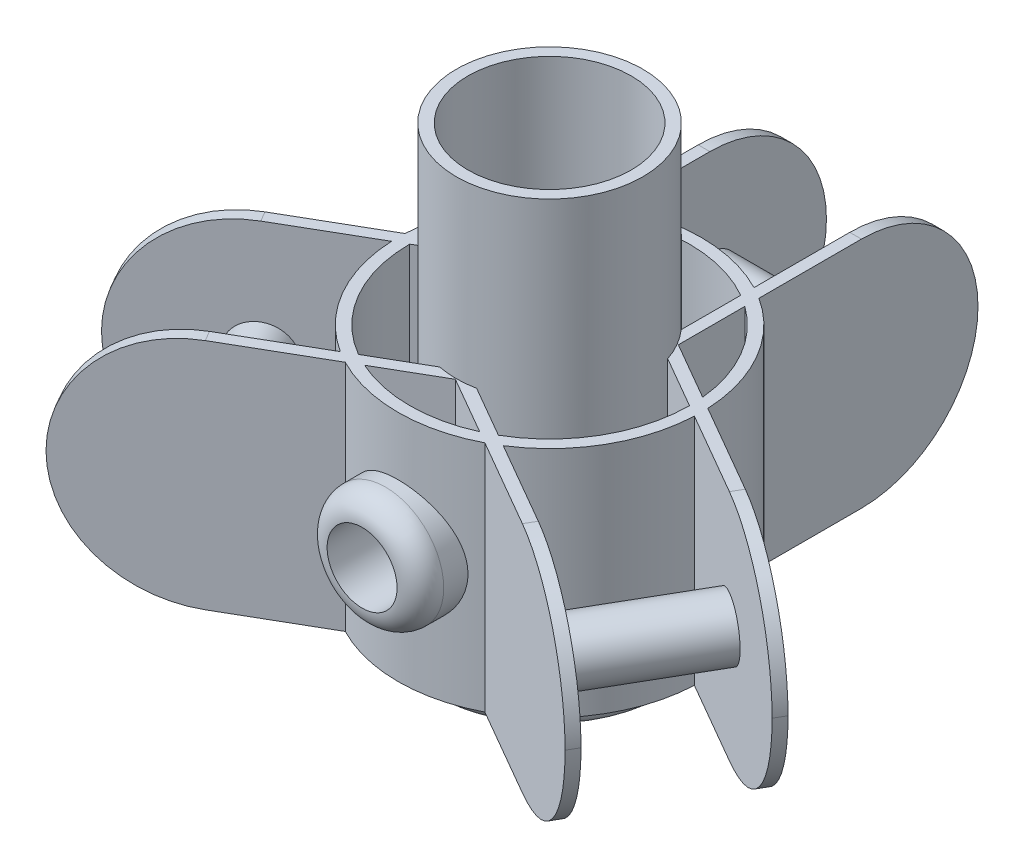
SolidWorks part; units mm, degrees
material "Rubber"
ref_plane "Front Plane" through (0, 0, 0) normal (0, 0, 1) x (1, 0, 0)
ref_plane "Top Plane" through (0, 0, 0) normal (0, 1, 0) x (1, 0, 0)
ref_plane "Right Plane" through (0, 0, 0) normal (1, 0, 0) x (0, 0, -1)
sketch "Sketch1" plane through (0, 0, 0) normal (0, 1, 0) x (1, 0, 0)
  line L0 (-6, 11.5326) -> (-6, 29.7468)
  line L1 (-6, 29.7468) -> (-7, 29.7468)
  line L2 (-7, 4.0415) -> (-7, 9.7468)
  line L3 (-7, 10.9545) -> (-7, 29.7468)
  line L4 (6, 10.3923) -> (6, 5.2915)
  line L5 (7, 4.0415) -> (7, 9.7468)
  line L6 (7, 10.9545) -> (7, 29.7468)
  line L7 (7, 29.7468) -> (6, 29.7468)
  line L8 (-29.2615, -8.8112) -> (-28.7615, -9.6772)
  line L9 (-6, 5.2915) -> (-6, 10.3923)
  line L10 (7, 29.7468) -> (6, 29.7468)
  line L11 (6, 29.7468) -> (6, 11.5326)
  line L12 (7.5826, 2.5504) -> (12, 0)
  line L13 (0, -8.0829) -> (4.941, -10.9356)
  line L14 (7, 4.0415) -> (11.941, 1.1888)
  line L15 (12.9868, 0.585) -> (29.2615, -8.8112)
  line L16 (12.9875, -0.5701) -> (28.7615, -9.6772)
  line L17 (22.7615, -20.0695) -> (6.9875, -10.9624)
  line L18 (5.9868, -11.5394) -> (22.2615, -20.9356)
  line L19 (6, -10.3923) -> (1.5826, -7.8419)
  line L20 (-1.5826, -7.8419) -> (-6, -10.3923)
  line L21 (-7, 4.0415) -> (-11.941, 1.1888)
  line L22 (0, -8.0829) -> (-4.941, -10.9356)
  line L23 (-5.9868, -11.5394) -> (-22.2615, -20.9356)
  line L24 (-6.9875, -10.9624) -> (-22.7615, -20.0695)
  line L25 (-28.7615, -9.6772) -> (-12.9875, -0.5701)
  line L26 (-12.9868, 0.585) -> (-29.2615, -8.8112)
  line L27 (-12, 0) -> (-7.5826, 2.5504)
  line L28 (-22.7615, -20.0695) -> (-22.2615, -20.9356)
  line L29 (22.2615, -20.9356) -> (22.7615, -20.0695)
  line L30 (28.7615, -9.6772) -> (29.2615, -8.8112)
  circle A0 centre (0, 0) radius 7
  arc A1 (-7.5826, 2.5504) -> (-1.5826, -7.8419) centre (0, 0) ccw
  arc A2 (-7, 9.7468) -> (-11.941, 1.1888) centre (0, 0) ccw
  arc A3 (-7, 10.9545) -> (-12.9868, 0.585) centre (0, 0) ccw
  arc A4 (6, 5.2915) -> (-6, 5.2915) centre (0, 0) ccw
  arc A5 (6, 10.3923) -> (-6, 10.3923) centre (0, 0) ccw
  arc A6 (6, 11.5326) -> (-6, 11.5326) centre (0, 0) ccw
  arc A7 (6, 5.2915) -> (-6, 5.2915) centre (0, 0) ccw
  arc A8 (11.941, 1.1888) -> (7, 9.7468) centre (0, 0) ccw
  arc A9 (1.5826, -7.8419) -> (7.5826, 2.5504) centre (0, 0) ccw
  arc A10 (-4.941, -10.9356) -> (4.941, -10.9356) centre (0, 0) ccw
  arc A11 (-5.9868, -11.5394) -> (5.9868, -11.5394) centre (0, 0) ccw
  arc A12 (-4.941, -10.9356) -> (4.941, -10.9356) centre (0, 0) ccw
  arc A13 (-4.941, -10.9356) -> (4.941, -10.9356) centre (0, 0) ccw
  arc A14 (6, -10.3923) -> (12, 0) centre (0, 0) ccw
  arc A15 (6, -10.3923) -> (12, 0) centre (0, 0) ccw
  arc A16 (6.9875, -10.9624) -> (12.9875, -0.5701) centre (0, 0) ccw
  arc A17 (1.5826, -7.8419) -> (7.5826, 2.5504) centre (0, 0) ccw
  arc A18 (-12, 0) -> (-6, -10.3923) centre (0, 0) ccw
  arc A19 (-12, 0) -> (-6, -10.3923) centre (0, 0) ccw
  arc A20 (-12.9875, -0.5701) -> (-6.9875, -10.9624) centre (0, 0) ccw
  arc A21 (-7.5826, 2.5504) -> (-1.5826, -7.8419) centre (0, 0) ccw
  arc A22 (6, 5.2915) -> (-6, 5.2915) centre (0, 0) ccw
  arc A23 (6, 10.3923) -> (-6, 10.3923) centre (0, 0) ccw
  arc A24 (6, 10.3923) -> (-6, 10.3923) centre (0, 0) ccw
  arc A25 (-7, 9.7468) -> (-11.941, 1.1888) centre (0, 0) ccw
  arc A26 (-7, 9.7468) -> (-11.941, 1.1888) centre (0, 0) ccw
  arc A27 (11.941, 1.1888) -> (7, 9.7468) centre (0, 0) ccw
  arc A28 (11.941, 1.1888) -> (7, 9.7468) centre (0, 0) ccw
  arc A29 (12.9868, 0.585) -> (7, 10.9545) centre (0, 0) ccw
  dimension "D1" = 3
extrude "Boss-Extrude1" add sketch "Sketch1" along normal blind 20 contours L15 A29 L6 L7 L11 A6 L0 L1 L3 A3 L26 L8 L25 A20 L24 L28 L23 A11 L18 L29 L17 A16 L16 L30 A0 A2 L2 L21 A5 L4 A4 L9 A8 L14 L5 A10 L22 L13 A14 L19 A9 L12 A18 L27 region at (0, 0, -12.2258)
fillet "Fillet1" radius 10 12 edges at (29.0115, 20, 9.2442) (29.0115, 0, 9.2442) (22.5115, 0, 20.5026) (22.5115, 20, 20.5026) (-29.0115, 0, 9.2442) (-22.5115, 0, 20.5026) (-22.5115, 20, 20.5026) (-29.0115, 20, 9.2442) (6.5, 0, -29.7468) (6.5, 20, -29.7468) (-6.5, 0, -29.7468) (-6.5, 20, -29.7468)
sketch "Sketch2" plane through (0, 0, 0) normal (0, -1, 0) x (1, 0, 0)
  circle A0 centre (0, 0) radius 13
extrude "Boss-Extrude2" add sketch "Sketch2" against normal blind 1
sketch "Sketch3" plane through (0, 20, 0) normal (0, 1, 0) x (1, 0, 0)
  circle A0 centre (0, 0) radius 7
  circle A1 centre (0, 0) radius 8
extrude "Boss-Extrude3" add sketch "Sketch3" along normal blind 15
sketch "Sketch4" plane through (-3, 0, -5.1962) normal (0.5, 0, 0.866) x (0.866, 0, -0.5)
  circle A0 centre (-19.7468, 10) radius 2.5
extrude "Boss-Extrude4" add sketch "Sketch4" along normal blind 12
pattern_circular "CirPattern1" count 3 every 120 about axis through (0, 0, 0) along (0, 1, 0) of "Boss-Extrude4"
ref_plane "Plane1" through (0, 0, 0) normal (-0.5, 0, 0.866) x (0.866, 0, 0.5)
ref_plane "Plane2" through (0, 0, 8.0829) normal (0, 0, -1) x (0, -1, 0)
ref_plane "Plane3" through (0, 0, 16.0829) normal (0, 0, -1) x (0, -1, 0)
sketch "Sketch5" plane through (0, 0, 16.0829) normal (0, 0, -1) x (0, -1, 0)
  circle A0 centre (-10, 0) radius 5
extrude "Boss-Extrude5" add sketch "Sketch5" along normal up to surface (4.0829 mm away) up to face at (0, 10, 12.2697)
fillet "Fillet2" radius 2 1 edges at (-5, 10, 16.0829)
sketch "Sketch6" plane through (0, 0, 16.0829) normal (0, 0, 1) x (1, 0, 0)
  circle A0 centre (0, 10) radius 3
extrude "Cut-Extrude1" cut sketch "Sketch6" against normal blind 12
cosmetic thread "Cosmetic Thread1" parameters "D2"=7
sketch "Sketch7" plane through (0, 0, 0) normal (0, -1, 0) x (1, 0, 0)
  circle A0 centre (0, 0) radius 6
  circle A1 centre (0, 0) radius 10
extrude "Boss-Extrude6" add sketch "Sketch7" along normal blind 3
fillet "Fillet3" radius 1 1 edges at (0, -3, -10)
sketch "Sketch8" plane through (0, -3, 0) normal (0, -1, 0) x (1, 0, 0)
  line L0 (4.7799, 6.4105) -> (3.5866, 4.81)
  line L1 (0, 8.5) -> (-0.4377, 8.5)
  line L2 (0, 8.5) -> (0.4377, 8.5)
  line L3 (0.9343, 7.9416) -> (0.701, 5.9589)
  line L4 (-0.9343, 7.9416) -> (-0.701, 5.9589)
  line L5 (4.25, 7.3612) -> (3.8709, 7.5801)
  line L6 (4.25, 7.3612) -> (4.6291, 7.1424)
  line L7 (3.1617, 7.3448) -> (2.3723, 5.5111)
  line L8 (7.3448, 3.1617) -> (5.5111, 2.3723)
  line L9 (7.3612, 4.25) -> (7.1424, 4.6291)
  line L10 (7.3612, 4.25) -> (7.5801, 3.8709)
  line L11 (6.4105, 4.7799) -> (4.81, 3.5866)
  line L12 (7.9416, -0.9343) -> (5.9589, -0.701)
  line L13 (8.5, 0) -> (8.5, 0.4377)
  line L14 (8.5, 0) -> (8.5, -0.4377)
  line L15 (7.9416, 0.9343) -> (5.9589, 0.701)
  line L16 (6.4105, -4.7799) -> (4.81, -3.5866)
  line L17 (7.3612, -4.25) -> (7.5801, -3.8709)
  line L18 (7.3612, -4.25) -> (7.1424, -4.6291)
  line L19 (7.3448, -3.1617) -> (5.5111, -2.3723)
  line L20 (3.1617, -7.3448) -> (2.3723, -5.5111)
  line L21 (4.25, -7.3612) -> (4.6291, -7.1424)
  line L22 (4.25, -7.3612) -> (3.8709, -7.5801)
  line L23 (4.7799, -6.4105) -> (3.5866, -4.81)
  line L24 (-0.9343, -7.9416) -> (-0.701, -5.9589)
  line L25 (0, -8.5) -> (0.4377, -8.5)
  line L26 (0, -8.5) -> (-0.4377, -8.5)
  line L27 (0.9343, -7.9416) -> (0.701, -5.9589)
  line L28 (-4.7799, -6.4105) -> (-3.5866, -4.81)
  line L29 (-4.25, -7.3612) -> (-3.8709, -7.5801)
  line L30 (-4.25, -7.3612) -> (-4.6291, -7.1424)
  line L31 (-3.1617, -7.3448) -> (-2.3723, -5.5111)
  line L32 (-7.3448, -3.1617) -> (-5.5111, -2.3723)
  line L33 (-7.3612, -4.25) -> (-7.1424, -4.6291)
  line L34 (-7.3612, -4.25) -> (-7.5801, -3.8709)
  line L35 (-6.4105, -4.7799) -> (-4.81, -3.5866)
  line L36 (-7.9416, 0.9343) -> (-5.9589, 0.701)
  line L37 (-8.5, 0) -> (-8.5, -0.4377)
  line L38 (-8.5, 0) -> (-8.5, 0.4377)
  line L39 (-7.9416, -0.9343) -> (-5.9589, -0.701)
  line L40 (-6.4105, 4.7799) -> (-4.81, 3.5866)
  line L41 (-7.3612, 4.25) -> (-7.5801, 3.8709)
  line L42 (-7.3612, 4.25) -> (-7.1424, 4.6291)
  line L43 (-7.3448, 3.1617) -> (-5.5111, 2.3723)
  line L44 (-3.1617, 7.3448) -> (-2.3723, 5.5111)
  line L45 (-4.25, 7.3612) -> (-4.6291, 7.1424)
  line L46 (-4.25, 7.3612) -> (-3.8709, 7.5801)
  line L47 (-4.7799, 6.4105) -> (-3.5866, 4.81)
  arc A0 (0.701, 5.9589) -> (-0.701, 5.9589) centre (0, 0) ccw
  circle A1 centre (0, 0) radius 6 construction
  arc A2 (-0.4377, 8.5) -> (-0.9343, 7.9416) centre (-0.4377, 8) ccw
  arc A3 (0.4377, 8.5) -> (0.9343, 7.9416) centre (0.4377, 8) cw
  arc A4 (4.6291, 7.1424) -> (4.7799, 6.4105) centre (4.3791, 6.7093) cw
  arc A5 (3.8709, 7.5801) -> (3.1617, 7.3448) centre (3.6209, 7.1471) ccw
  arc A6 (7.5801, 3.8709) -> (7.3448, 3.1617) centre (7.1471, 3.6209) cw
  arc A7 (7.1424, 4.6291) -> (6.4105, 4.7799) centre (6.7093, 4.3791) ccw
  arc A8 (8.5, -0.4377) -> (7.9416, -0.9343) centre (8, -0.4377) cw
  arc A9 (8.5, 0.4377) -> (7.9416, 0.9343) centre (8, 0.4377) ccw
  arc A10 (7.1424, -4.6291) -> (6.4105, -4.7799) centre (6.7093, -4.3791) cw
  arc A11 (7.5801, -3.8709) -> (7.3448, -3.1617) centre (7.1471, -3.6209) ccw
  arc A12 (3.8709, -7.5801) -> (3.1617, -7.3448) centre (3.6209, -7.1471) cw
  arc A13 (4.6291, -7.1424) -> (4.7799, -6.4105) centre (4.3791, -6.7093) ccw
  arc A14 (-0.4377, -8.5) -> (-0.9343, -7.9416) centre (-0.4377, -8) cw
  arc A15 (0.4377, -8.5) -> (0.9343, -7.9416) centre (0.4377, -8) ccw
  arc A16 (-4.6291, -7.1424) -> (-4.7799, -6.4105) centre (-4.3791, -6.7093) cw
  arc A17 (-3.8709, -7.5801) -> (-3.1617, -7.3448) centre (-3.6209, -7.1471) ccw
  arc A18 (-7.5801, -3.8709) -> (-7.3448, -3.1617) centre (-7.1471, -3.6209) cw
  arc A19 (-7.1424, -4.6291) -> (-6.4105, -4.7799) centre (-6.7093, -4.3791) ccw
  arc A20 (-8.5, 0.4377) -> (-7.9416, 0.9343) centre (-8, 0.4377) cw
  arc A21 (-8.5, -0.4377) -> (-7.9416, -0.9343) centre (-8, -0.4377) ccw
  arc A22 (-7.1424, 4.6291) -> (-6.4105, 4.7799) centre (-6.7093, 4.3791) cw
  arc A23 (-7.5801, 3.8709) -> (-7.3448, 3.1617) centre (-7.1471, 3.6209) ccw
  arc A24 (-3.8709, 7.5801) -> (-3.1617, 7.3448) centre (-3.6209, 7.1471) cw
  arc A25 (-4.6291, 7.1424) -> (-4.7799, 6.4105) centre (-4.3791, 6.7093) ccw
  arc A26 (5.9589, -0.701) -> (5.9589, 0.701) centre (0, 0) ccw
  arc A27 (4.81, -3.5866) -> (5.5111, -2.3723) centre (0, 0) ccw
  arc A28 (2.3723, -5.5111) -> (3.5866, -4.81) centre (0, 0) ccw
  arc A29 (-0.701, -5.9589) -> (0.701, -5.9589) centre (0, 0) ccw
  arc A30 (-3.5866, -4.81) -> (-2.3723, -5.5111) centre (0, 0) ccw
  arc A31 (-5.5111, -2.3723) -> (-4.81, -3.5866) centre (0, 0) ccw
  arc A32 (-5.9589, 0.701) -> (-5.9589, -0.701) centre (0, 0) ccw
  arc A33 (-4.81, 3.5866) -> (-5.5111, 2.3723) centre (0, 0) ccw
  arc A34 (3.5866, 4.81) -> (2.3723, 5.5111) centre (0, 0) ccw
  arc A35 (5.5111, 2.3723) -> (4.81, 3.5866) centre (0, 0) ccw
  arc A36 (-2.3723, 5.5111) -> (-3.5866, 4.81) centre (0, 0) ccw
  dimension "D1" = 0.5
  dimension "D2" = 12
extrude "Boss-Extrude7" add sketch "Sketch8" along normal blind 0.25
sketch "Sketch9" plane through (0, 0, 0) normal (0, -1, 0) x (1, 0, 0)
  circle A0 centre (0, 0) radius 6
extrude "Cut-Extrude2" cut sketch "Sketch9" against normal blind 10.25
fillet "Fillet4" radius 1 1 edges at (0, 1, -6)
